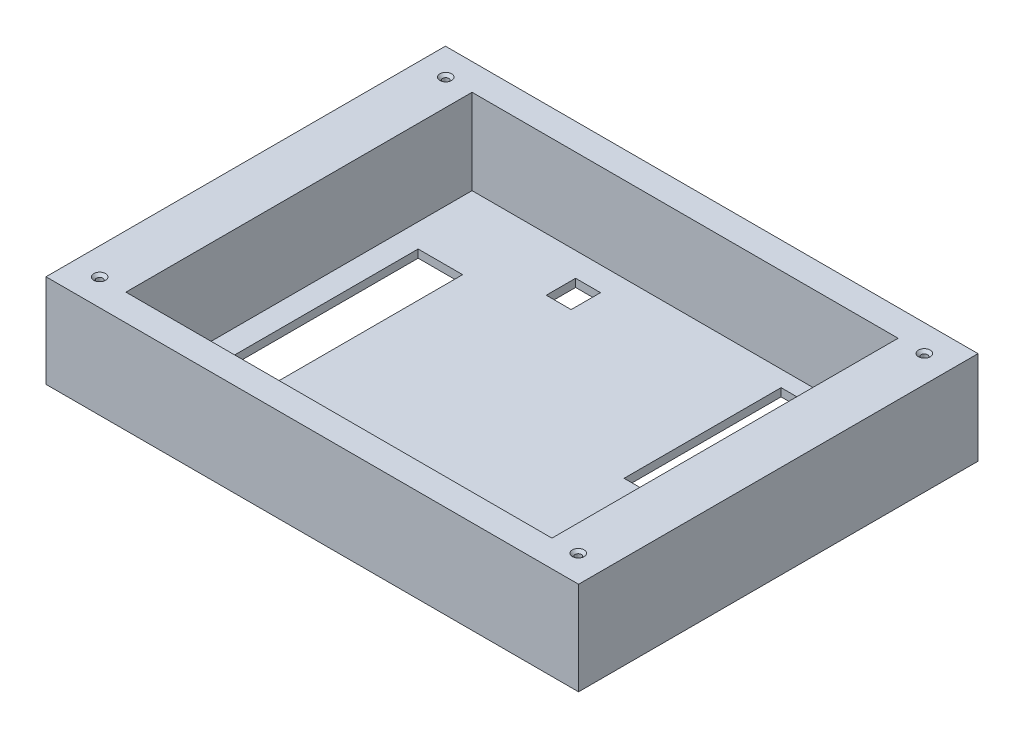
SolidWorks part; units mm, degrees
ref_plane "Front Plane" through (0, 0, 0) normal (0, 0, 1) x (1, 0, 0)
ref_plane "Top Plane" through (0, 0, 0) normal (0, 1, 0) x (1, 0, 0)
ref_plane "Right Plane" through (0, 0, 0) normal (1, 0, 0) x (0, 0, -1)
sketch "Sketch6" plane through (0, 0, 0) normal (0, 1, 0) x (1, 0, 0)
  line L1 (-100, 75) -> (100, 75)
  line L2 (-100, 75) -> (-100, -75)
  line L3 (-100, -75) -> (100, -75)
  line L4 (100, 75) -> (100, -75)
  line L5 (-100, 75) -> (100, -75) construction
  line L6 (-100, -75) -> (100, 75) construction
  point P0 (0, 0)
  point P6 (0, 0)
  dimension "D1" = 200
  dimension "D2" = 150
extrude "Boss-Extrude1" add sketch "Sketch6" along normal blind 35
sketch "Sketch7" plane through (0, 35, 0) normal (0, 1, 0) x (1, 0, 0)
  line L1 (-80, -65) -> (80, -65)
  line L2 (-80, -65) -> (-80, 65)
  line L3 (-80, 65) -> (80, 65)
  line L4 (80, -65) -> (80, 65)
  line L5 (-80, -65) -> (80, 65) construction
  line L6 (-80, 65) -> (80, -65) construction
  point P0 (0, 0)
  dimension "D1" = 160
  dimension "D2" = 130
extrude "Cut-Extrude1" cut sketch "Sketch7" against normal blind 32
sketch "Sketch8" plane through (0, 0, 0) normal (0, -1, 0) x (1, 0, 0)
  line L1 (-71.1532, 44.9301) -> (-54.4506, 44.9301)
  line L2 (-71.1532, 44.9301) -> (-71.1532, -35.9107)
  line L3 (-71.1532, -35.9107) -> (-54.4506, -35.9107)
  line L4 (-54.4506, 44.9301) -> (-54.4506, -35.9107)
  line L5 (-32.0691, -44.9301) -> (-22.7156, -44.9301)
  line L6 (-32.0691, -44.9301) -> (-32.0691, -55.9538)
  line L7 (-32.0691, -55.9538) -> (-22.7156, -55.9538)
  line L8 (-22.7156, -44.9301) -> (-22.7156, -55.9538)
  line L9 (42.0906, 0) -> (56.789, 0)
  line L10 (42.0906, 0) -> (42.0906, -58.9603)
  line L11 (42.0906, -58.9603) -> (56.789, -58.9603)
  line L12 (56.789, 0) -> (56.789, -58.9603)
  line L13 (71.4873, -7.5162) -> (84.8494, -7.5162)
  line L14 (71.4873, -7.5162) -> (71.4873, -20.8783)
  line L15 (71.4873, -20.8783) -> (84.8494, -20.8783)
  line L16 (84.8494, -7.5162) -> (84.8494, -20.8783)
extrude "Cut-Extrude2" cut sketch "Sketch8" against normal blind 32
hole_wizard "CSK for M2 Flat Head Machine Screw2" positions "Sketch11" profile "Sketch12" countersink size "M2" standard "ANSI Metric"
sketch "Sketch11" plane through (0, 35, 0) normal (0, 1, 0) x (1, 0, 0)
  point P0 (-89.8602, -64.9732)
  point P2 (-89.8602, 64.9732)
  point P4 (89.8602, 65)
  point P6 (89.8602, -64.9732)
sketch "Sketch12" plane through (-89.8602, 35, 64.9732) normal (1, 0, 0) x (0, 0, 1)
  line L0 (0, 0) -> (0, 10)
  line L1 (0, 10) -> (1.2, 9.279)
  line L2 (1.2, 9.279) -> (1.2, 1)
  line L3 (1.2, 1) -> (2.2, 0)
  line L5 (2.2, 0) -> (0, 0)
  line L6 (-1.2, 1) -> (-2.2, 0) construction
  line L10 (0, 10) -> (-1.2, 9.279) construction
  line L11 (0, -6.35) -> (0, 107.95) construction
  dimension "Hole Dia." = 2.4
  dimension "Hole Depth" = 10
  dimension "Near C'Sink Dia." = 4.4
  dimension "Near C'Sink Angle" = 90
  dimension "Drill Angle" = 118
